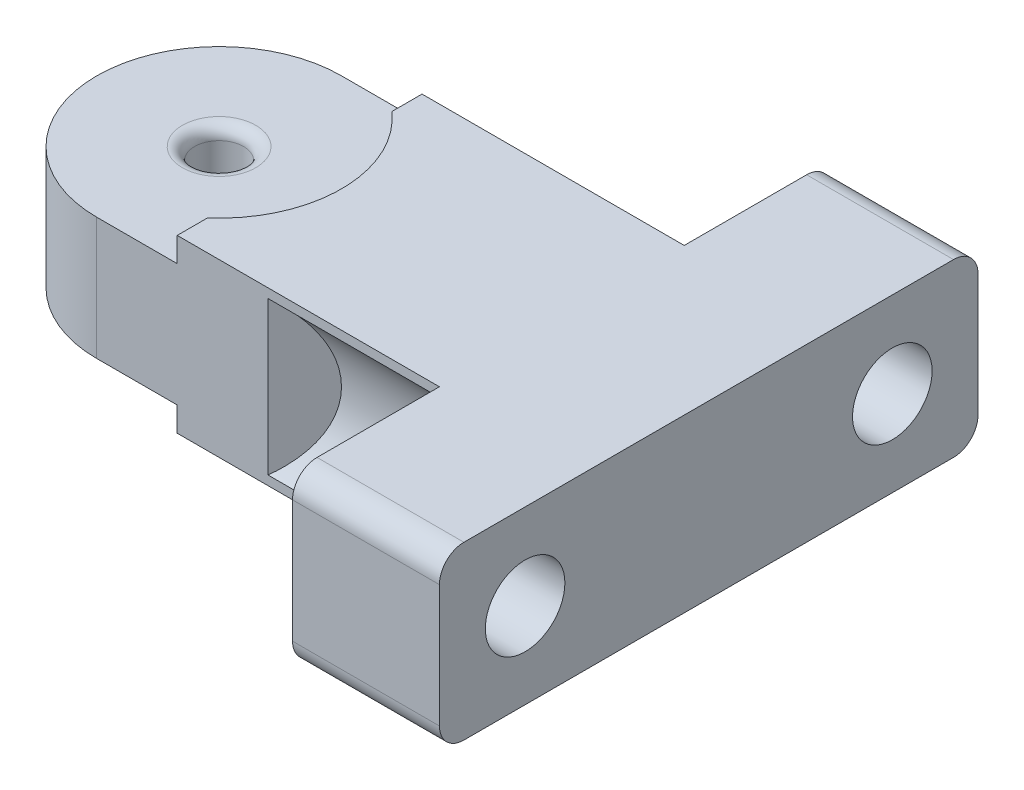
SolidWorks part; units mm, degrees
ref_plane "Front" through (0, 0, 0) normal (0, 0, 1) x (1, 0, 0)
ref_plane "Top" through (0, 0, 0) normal (0, 1, 0) x (1, 0, 0)
ref_plane "Right" through (0, 0, 0) normal (1, 0, 0) x (0, 0, -1)
sketch "Sketch1" plane through (0, 0, 0) normal (0, 1, 0) x (1, 0, 0)
  line L1 (25, -10) -> (-25, -10)
  line L2 (25, -10) -> (25, 10)
  line L3 (25, 10) -> (-25, 10)
  line L4 (-25, -10) -> (-25, 10)
  line L5 (25, -10) -> (-25, 10) construction
  line L6 (25, 10) -> (-25, -10) construction
  point P0 (0, 0)
  dimension "D1" = 50
  dimension "D2" = 20
extrude "Boss-Extrude1" add sketch "Sketch1" along normal blind 10
sketch "Sketch2" plane through (0, 10, 0) normal (0, 1, 0) x (1, 0, 0)
  circle A1 centre (-15, 0) radius 2
  dimension "D2" = 4
fillet "Fillet1" radius 10 2 edges at (-25, 5, 10) (-25, 5, -10)
extrude "Cut-Extrude1" cut sketch "Sketch2" against normal blind 10
sketch "Sketch6" plane through (0, 10, 0) normal (0, 1, 0) x (1, 0, 0)
  line L0 (-8.4202, 10) -> (-8.4202, 7.5304)
  line L1 (25, 10) -> (-8.4202, 10)
  line L2 (25, 10) -> (25, -10)
  line L3 (25, -10) -> (-8.4202, -10)
  line L5 (8.2899, -10) -> (8.2899, 10) construction
  line L6 (25, 0) -> (-15, 0) construction
  line L7 (-8.4202, -7.5304) -> (-8.4202, -10)
  arc A0 (-8.4202, -7.5304) -> (-8.4202, 7.5304) centre (-15, 0) ccw
  point P287 (8.2899, 0)
extrude "Boss-Extrude3" add sketch "Sketch6" along normal blind 2
ref_plane "Plane1" through (0, 5, 0) normal (0, -1, 0) x (-1, 0, 0)
mirror "Mirror3" about plane through (0, 5, 0) normal (0, -1, 0) of "Boss-Extrude3"
fillet "Fillet4" radius 1 2 edges at (-15, 10, 2) (-15, 0, 2)
sketch "Sketch9" plane through (25, 0, 0) normal (1, 0, 0) x (0, 0, -1)
  line L1 (-10, -2) -> (-22, -2)
  line L2 (-10, -2) -> (-10, 12)
  line L3 (-10, 12) -> (-22, 12)
  line L4 (-22, -2) -> (-22, 12)
  line L5 (-16, 12) -> (-16, -2) construction
  line L6 (-10, 5) -> (-22, 5) construction
  line L7 (10, -2) -> (22, -2)
  line L8 (10, -2) -> (10, 12)
  line L9 (10, 12) -> (22, 12)
  line L10 (22, -2) -> (22, 12)
  line L11 (16, 12) -> (16, -2) construction
  line L12 (10, 5) -> (22, 5) construction
  point P200 (16, 5)
  point P280 (-16, 5)
  dimension "D1" = 12
extrude "Boss-Extrude4" add sketch "Sketch9" against normal blind 12
sketch "Sketch10" plane through (25, 0, 0) normal (1, 0, 0) x (0, 0, -1)
  line L0 (0, 50) -> (0, -50) construction
  circle A0 centre (-15, 5) radius 3.25
  circle A1 centre (15, 5) radius 3.25
  dimension "D1" = 6.5
  dimension "D2" = 30
  dimension "D3" = 15
extrude "Cut-Extrude4" cut sketch "Sketch10" against normal blind 18
sketch "Sketch13" plane through (13, 0, 0) normal (-1, 0, 0) x (0, 0, 1)
  circle A0 centre (15, 5) radius 8
  dimension "D1" = 16
extrude "Cut-Extrude5" cut sketch "Sketch13" along normal blind 10 contours A0
mirror "Mirror7" about plane through (0, 0, 0) normal (0, 0, 1) of "Cut-Extrude5"
chamfer "Chamfer4" distance 4 angle 45 2 edges at (3, 5, 10) (3, 5, -10)
fillet "Fillet6" radius 2 4 edges at (19, -2, -22) (19, 12, -22) (19, -2, 22) (19, 12, 22)
sketch "Sketch14" plane through (0, 0, 0) normal (0, -1, 0) x (1, 0, 0)
  line L0 (-15, 0) -> (-25, 0)
  line L1 (-25, 0) -> (-15, 0)
  line L2 (-15, 0) -> (-24.6126, -2.7564)
  circle A0 centre (-15, 0) radius 10
  circle M3 centre (-15, 0) radius 3
  arc M10 (-25, 0) -> (-15, -10) centre (-15, 0) ccw
  dimension "D1" = 16
extrude "Boss-Extrude5" add sketch "Sketch14" along normal blind 1 contours L2 L0 M3 M10 region at (-22.0359, 0, -0.9888)
